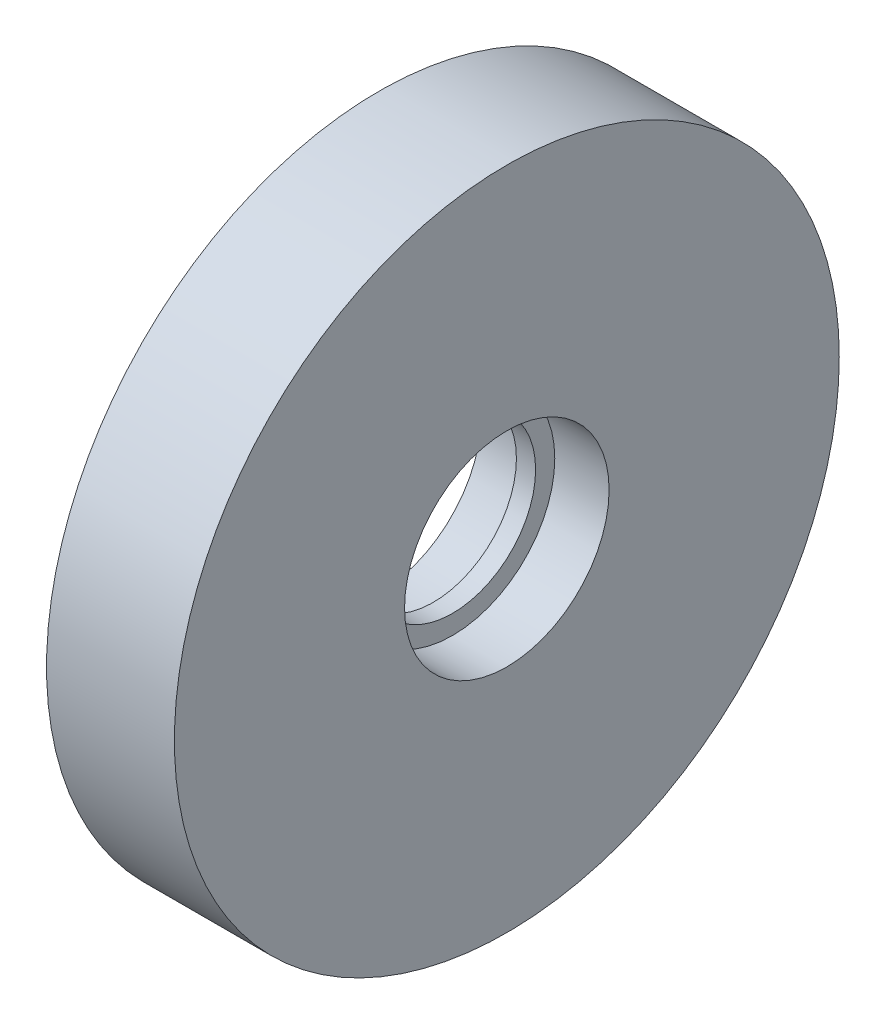
SolidWorks part; units mm, degrees
ref_plane "Front Plane" through (0, 0, 0) normal (0, 0, 1) x (1, 0, 0)
ref_plane "Top Plane" through (0, 0, 0) normal (0, 1, 0) x (1, 0, 0)
ref_plane "Right Plane" through (0, 0, 0) normal (1, 0, 0) x (0, 0, -1)
sketch "Sketch1" plane through (0, 0, 0) normal (1, 0, 0) x (0, 0, -1)
  circle A0 centre (0, 0) radius 26
  circle A2 centre (0, 0) radius 8
  dimension "D1" = 52
  dimension "D2" = 16
extrude "Boss-Extrude1" add sketch "Sketch1" along normal blind 10
ref_plane "Plane1" through (5, 0, 0) normal (1, 0, 0) x (0, 0, -1)
sketch "Sketch2" plane through (5, 0, 0) normal (1, 0, 0) x (0, 0, -1)
  circle A0 centre (0, 0) radius 6.5
  circle A1 centre (0, 0) radius 8 construction
  circle A2 centre (0, 0) radius 8
  dimension "D1" = 13
extrude "Boss-Extrude2" add sketch "Sketch2" along normal mid plane 1.5
